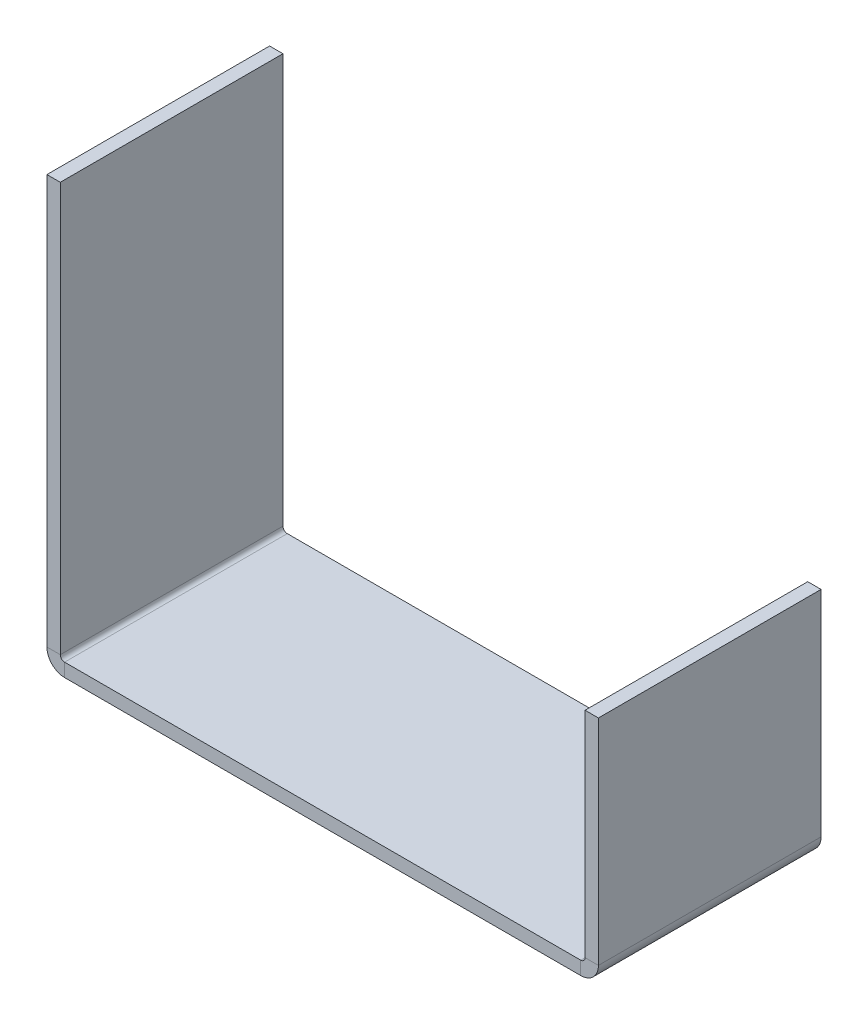
SolidWorks part; units mm, degrees
note: The reader was unsure of these and kept them because the rebuilt part matched: flange length of "Edge-Flange1", "Edge-Flange2".
ref_plane "Front Plane" through (0, 0, 0) normal (0, 0, 1) x (1, 0, 0)
ref_plane "Top Plane" through (0, 0, 0) normal (0, 1, 0) x (1, 0, 0)
ref_plane "Right Plane" through (0, 0, 0) normal (1, 0, 0) x (0, 0, -1)
sketch "Sketch1" plane through (0, 0, 0) normal (0, 1, 0) x (1, 0, 0)
  line L1 (-47.1805, -19.05) -> (47.1805, -19.05)
  line L2 (-47.1805, -19.05) -> (-47.1805, 19.05)
  line L3 (-47.1805, 19.05) -> (47.1805, 19.05)
  line L4 (47.1805, -19.05) -> (47.1805, 19.05)
  line L5 (-47.1805, -19.05) -> (47.1805, 19.05) construction
  line L6 (-47.1805, 19.05) -> (47.1805, -19.05) construction
  point P0 (0, 0)
  dimension "D1" = 94.361
  dimension "D2" = 38.1
base flange "Base-Flange1" sketch "Sketch1" thickness 2.286 reverse thickness direction no parameters "D1"=0.7366
edge flange "Edge-Flange1" sketch "Sketch10" flange angle 90 flange length 39.6875 flange position material inside bend radius 0.7366 thickness 2.286 relief rectangular parameters "D6"=10, "D8"=0.254
sketch "Sketch10" plane through (47.1805, 0, 0) normal (1, 0, 0) x (0, 0, -1)
  line L2 (-19.05, 0) -> (-19.05, 37.4015)
  line L3 (-19.05, 37.4015) -> (19.05, 37.4015)
  line L4 (19.05, 37.4015) -> (19.05, 0)
  line L11 (-19.05, 0) -> (19.05, 0) construction
  line L12 (-19.05, 0) -> (19.05, 0)
bend "EdgeBend1" bend radius 0.7366 bend angle 90 parameters "D5"=1
edge flange "Edge-Flange2" sketch "Sketch14" flange angle 90 flange length 73.025 flange position material inside bend radius 0.7366 thickness 2.286 relief rectangular parameters "D6"=10
sketch "Sketch14" plane through (-47.1805, 0, 0) normal (-1, 0, 0) x (0, 0, 1)
  line L0 (-19.05, 0) -> (19.05, 0) construction
  line L1 (-19.05, 0) -> (19.05, 0)
  line L2 (-19.05, 0) -> (-19.05, 70.739)
  line L3 (-19.05, 70.739) -> (19.05, 70.739)
  line L4 (19.05, 70.739) -> (19.05, 0)
bend "EdgeBend3" bend radius 0.7366 bend angle 90 parameters "D5"=2
sketch "Bend-Lines1" [suppressed] plane through (0, 0, 0) normal (0, 1, 0) x (1, 0, 0)
sketch "Bounding-Box1" [suppressed] plane through (0, 0, 0) normal (0, 1, 0) x (1, 0, 0)
sheet metal parameters "Sheet-Metal1" thickness 2.286 parameters "D1"=0.7366
flat pattern "Flat-Pattern1" [suppressed]
sketch "Bend-Lines2" plane through (0, 0, 0) normal (0, 1, 0) x (1, 0, 0)
sketch3d "Bounding-Box2" [suppressed]
  line L0 (45.2437, -50.8, 0) -> (45.2437, 50.8, 0) construction
  line L1 (-45.2438, -50.8, 0) -> (-45.2438, 50.8, 0) construction
  line L2 (45.2437, -50.8, 0) -> (-45.2438, -50.8, 0) construction
  line L3 (45.2437, 50.8, 0) -> (-45.2438, 50.8, 0) construction
sheet metal parameters "Sheet-Metal2" thickness 2.286 parameters "D1"=0.7366
flat pattern "Flat-Pattern1"
sketch "Bend-Lines2" plane through (0, 0, 0) normal (0, 1, 0) x (1, 0, 0)
  line L1 (56.8579, -41.275) -> (56.8579, 41.275) construction
  line L3 (56.8579, -41.275) -> (56.8579, 41.275) construction
sketch3d "Bounding-Box2" [suppressed]
  line L0 (82.4103, 41.275, 0) -> (-47.1805, 41.275, 0) construction
  line L1 (82.4103, -41.275, 0) -> (-47.1805, -41.275, 0) construction
  line L2 (82.4103, 41.275, 0) -> (82.4103, -41.275, 0) construction
  line L3 (-47.1805, 41.275, 0) -> (-47.1805, -41.275, 0) construction
bend of the flat pattern "Flatten-<EdgeBend1>1"
sheet metal parameters "Sheet-Metal3" thickness 2.286 parameters "D1"=0.7366
flat pattern "Flat-Pattern1"
sketch "Bend-Lines2" plane through (0, 0, 0) normal (0, 1, 0) x (1, 0, 0)
  line L0 (-56.8579, 19.05) -> (-56.8579, -19.05) construction
  line L1 (56.8579, -19.05) -> (56.8579, 19.05) construction
  line L2 (-56.8579, 19.05) -> (-56.8579, -19.05) construction
  line L3 (56.8579, -19.05) -> (56.8579, 19.05) construction
sketch3d "Bounding-Box2" [suppressed]
  line L0 (106.2228, 19.05, 0) -> (-139.5603, 19.05, 0) construction
  line L1 (106.2228, -19.05, 0) -> (-139.5603, -19.05, 0) construction
  line L2 (106.2228, 19.05, 0) -> (106.2228, -19.05, 0) construction
  line L3 (-139.5603, 19.05, 0) -> (-139.5603, -19.05, 0) construction
bend of the flat pattern "Flatten-<EdgeBend1>1"
bend of the flat pattern "Flatten-<EdgeBend3>1"
